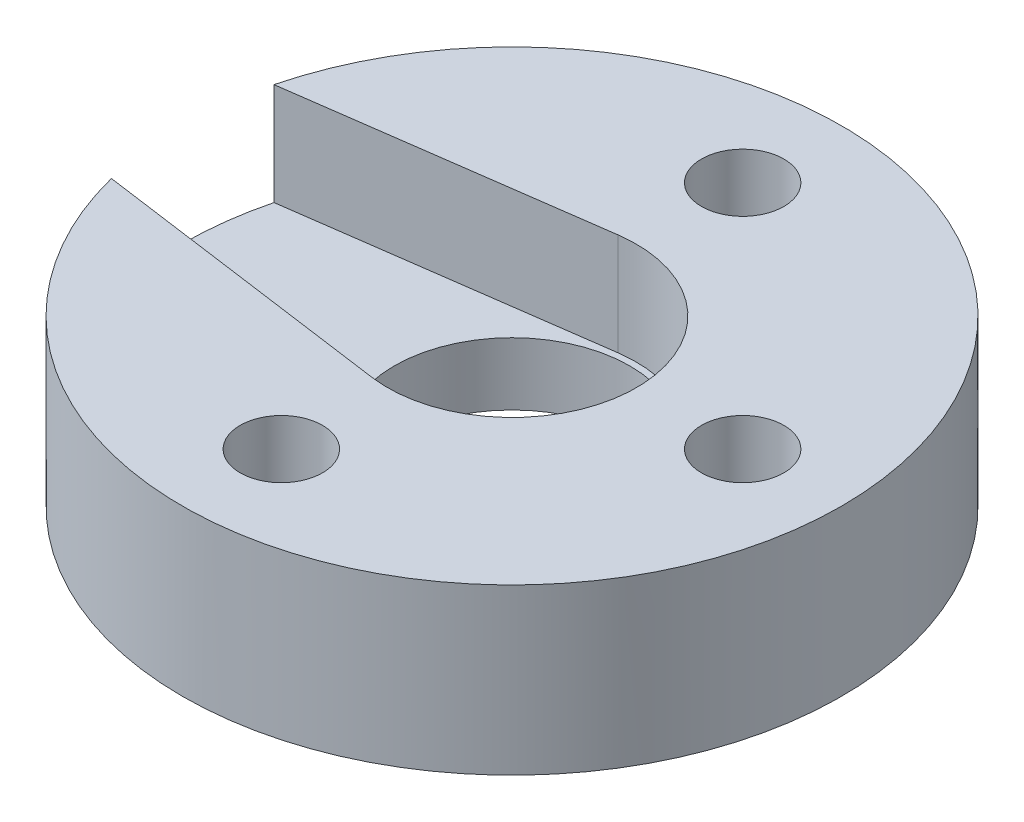
SolidWorks part; units mm, degrees
material "6061 Alloy"
ref_plane "Front Plane" through (0, 0, 0) normal (0, 0, 1) x (1, 0, 0)
ref_plane "Top Plane" through (0, 0, 0) normal (0, 1, 0) x (1, 0, 0)
ref_plane "Right Plane" through (0, 0, 0) normal (1, 0, 0) x (0, 0, -1)
sketch "Sketch1" plane through (0, 0, 0) normal (0, 1, 0) x (1, 0, 0)
  circle A0 centre (0, 0) radius 10
  dimension "D1" = 20
extrude "Boss-Extrude1" add sketch "Sketch1" along normal blind 5
ref_axis "Axis1" through (0, 5, 0) along (0, -1, 0)
hole_wizard "Tap Drill for M3x0.5 Tap1" positions "Sketch2" profile "Sketch3" hole size "M3x0.5" standard "ANSI Metric"
sketch "Sketch2" plane through (0, 5, 0) normal (0, 1, 0) x (1, 0, 0)
  point P0 (7, 0)
  dimension "D1" = 7
sketch "Sketch3" plane through (7, 5, 0) normal (1, 0, 0) x (0, 0, 1)
  line L0 (0, 0) -> (0, 38.1)
  line L1 (0, 38.1) -> (1.25, 38.1)
  line L2 (1.25, 38.1) -> (1.25, 0)
  line L5 (1.25, 0) -> (0, 0)
  line L10 (0, 38.1) -> (-1.25, 38.1) construction
  line L11 (0, -6.35) -> (0, 107.95) construction
  dimension "Hole Dia." = 2.5
  dimension "Hole Depth" = 38.1
  dimension "Drill Angle" = 180
pattern_circular "CirPattern1" count 4 over 360 about axis through (0, 5, 0) along (0, -1, 0) skipping 2 of "Tap Drill for M3x0.5 Tap1"
hole_wizard "#14 (0.182) Diameter Hole1" positions "Sketch7" profile "Sketch5" hole size "#14" standard "ANSI Inch" end condition through all
sketch "Sketch7" plane through (0, 5, 0) normal (0, 1, 0) x (1, 0, 0)
  point P0 (0, 0)
sketch "Sketch5" plane through (0, 5, 0) normal (1, 0, 0) x (0, 0, 1)
  line L0 (0, 0) -> (0, 5)
  line L1 (0, 5) -> (3.575, 5)
  line L2 (3.575, 5) -> (3.575, 0)
  line L5 (3.575, 0) -> (0, 0)
  line L11 (0, -6.35) -> (0, 107.95) construction
  dimension "Thru Hole Dia." = 7.15
  dimension "Thru Hole Depth" = 5
sketch "Sketch9" plane through (0, 5, 0) normal (0, 1, 0) x (1, 0, 0)
  line L0 (-0.5186, 3.7392) -> (-12.6601, 2.0553)
  line L3 (-0.5186, -3.7392) -> (-12.6601, -2.0553)
  arc A2 (-0.5186, -3.7392) -> (-0.5186, 3.7392) centre (0, 0) ccw
  arc A3 (-12.6601, 2.0553) -> (-12.6601, -2.0553) centre (-12.375, 0) ccw
  dimension "D2" = 12.375
  dimension "D3" = 2.075
  dimension "D1" = 3.775
extrude "Cut-Extrude2" cut sketch "Sketch9" against normal blind 3.1
